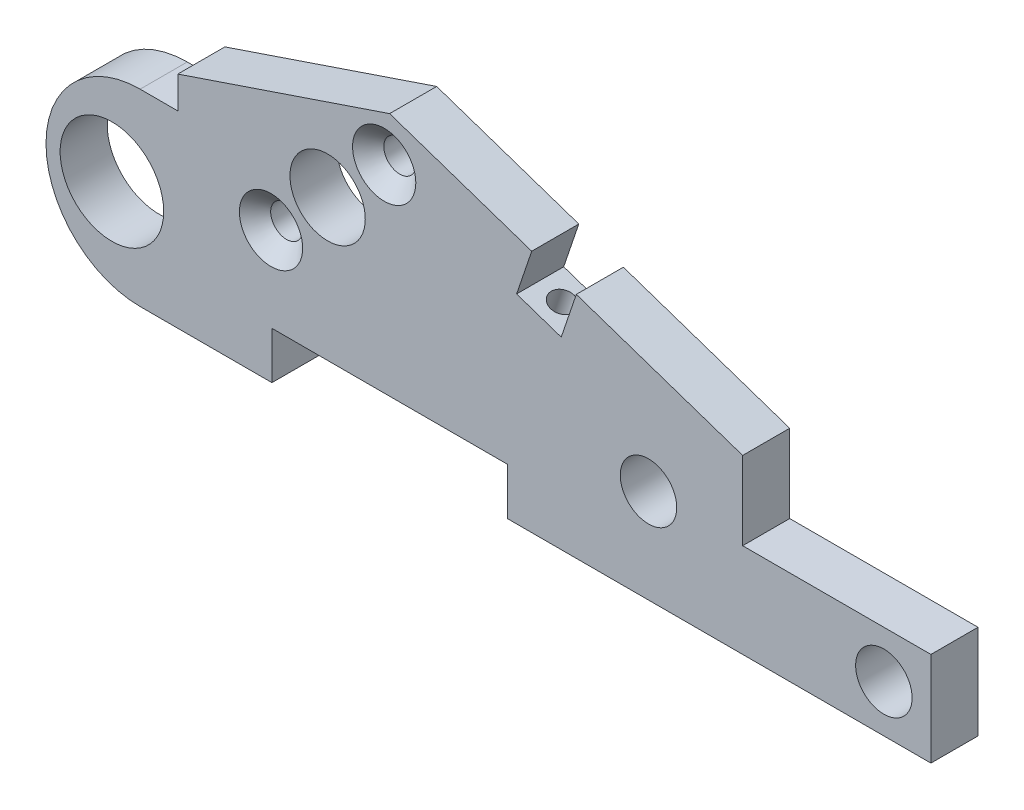
SolidWorks part; units mm, degrees
ref_plane "Front Plane" through (0, 0, 0) normal (0, 0, 1) x (1, 0, 0)
ref_plane "Top Plane" through (0, 0, 0) normal (0, 1, 0) x (1, 0, 0)
ref_plane "Right Plane" through (0, 0, 0) normal (1, 0, 0) x (0, 0, -1)
sketch "Sketch1" plane through (0, 0, 0) normal (0, 0, 1) x (1, 0, 0)
  line L0 (42.697, 5.7271) -> (5.197, 18.4194)
  line L1 (5.197, -12.5806) -> (5.197, 23.3572) construction
  line L2 (-31.303, -12.5806) -> (42.697, -12.5806)
  line L3 (42.697, -12.5806) -> (52.697, -12.5806)
  line L4 (52.697, -12.5806) -> (62.697, -12.5806)
  line L5 (-27.303, 7.4194) -> (-31.303, 7.4194)
  line L6 (-27.303, 7.4194) -> (-17.303, 7.4194)
  line L7 (-17.303, 7.4194) -> (-17.303, 10.8091)
  line L8 (-17.303, 10.8091) -> (5.197, 18.4194)
  line L9 (-31.303, 7.4194) -> (-31.303, -12.5806)
  line L10 (62.697, -12.5806) -> (62.697, -2.5806)
  line L11 (42.697, -2.5806) -> (42.697, 5.7271)
  line L12 (62.697, -2.5806) -> (52.697, -2.5806)
  line L16 (52.697, -2.5806) -> (42.697, -2.5806)
  dimension "D3" = 10
  dimension "D1" = 10
  dimension "D2" = 10
  dimension "D4" = 4
  dimension "D6" = 10
  dimension "D7" = 31
extrude "Boss-Extrude1" add sketch "Sketch1" along normal blind 5
sketch "Sketch2" plane through (0, 0, 5) normal (0, 0, 1) x (1, 0, 0)
  line L0 (-24.303, -2.5806) -> (-4.303, -2.5806) construction
  line L2 (-4.303, -2.5806) -> (-10.3134, -8.591) construction
  line L3 (-27.303, -2.5806) -> (-24.303, -2.5806) construction
  line L4 (-4.303, -2.5806) -> (-12.803, -2.5806) construction
  line L5 (-4.303, -2.5806) -> (1.7074, 3.4298) construction
  line L6 (-4.303, -2.5806) -> (4.197, -2.5806) construction
  line L7 (37.697, -2.5806) -> (32.697, -2.5806) construction
  circle A0 centre (-24.303, -2.5806) radius 25
  dimension "D6" = 8.5
  dimension "D8" = 50
  dimension "D1" = 3
  dimension "D2" = 20
  dimension "D3" = 8.5
  dimension "D4" = 8.5
  dimension "D5" = 8.5
  dimension "D7" = 5
hole_wizard "Ø11.0 (11) Diameter Hole1" positions "3DSketch2" profile "Sketch4" hole size "Ø11.0" standard "ISO"
sketch3d "3DSketch2"
  point P0 (-24.303, -2.5806, 5)
sketch "Sketch4" plane through (-24.303, -2.5806, 5) normal (1, 0, 0) x (0, -1, 0)
  line L0 (0, 0) -> (0, 28.3047)
  line L1 (0, 28.3047) -> (5.5, 25)
  line L2 (5.5, 25) -> (5.5, 0)
  line L5 (5.5, 0) -> (0, 0)
  line L10 (0, 28.3047) -> (-5.5, 25) construction
  line L11 (0, -6.35) -> (0, 107.95) construction
  dimension "Hole Dia." = 11
  dimension "Hole Depth" = 25
  dimension "Drill Angle" = 118
hole_wizard "Ø6.0mm Dowel Hole1" positions "3DSketch6" profile "Sketch9" hole size "Ø6.0" standard "ISO"
sketch3d "3DSketch6"
  point P0 (32.697, -2.5806, 5)
sketch "Sketch9" plane through (32.697, -2.5806, 5) normal (1, 0, 0) x (0, -1, 0)
  line L0 (0, 0) -> (0, 26.8026)
  line L1 (0, 26.8026) -> (3, 25)
  line L2 (3, 25) -> (3, 0)
  line L5 (3, 0) -> (0, 0)
  line L10 (0, 26.8026) -> (-3, 25) construction
  line L11 (0, -6.35) -> (0, 107.95) construction
  dimension "Hole Dia." = 6
  dimension "Hole Depth" = 25
  dimension "Drill Angle" = 118
sketch "Sketch22" plane through (0, 0, 0) normal (0, 0, -1) x (-1, 0, 0)
  line L0 (-37.697, -2.5806) -> (-17.697, -2.5806) construction
  line L1 (-17.697, -2.5806) -> (-17.697, -12.5806) construction
  line L3 (-17.697, -12.5806) -> (-17.697, -7.5806)
  line L4 (-17.697, -7.5806) -> (7.303, -7.5806)
  line L5 (7.303, -7.5806) -> (7.303, -12.5806)
  line L6 (7.303, -12.5806) -> (-17.697, -12.5806)
  dimension "D1" = 20
  dimension "D2" = 5
  dimension "D3" = 25
extrude "Cut-Extrude1" cut sketch "Sketch22" against normal blind 10
sketch "Sketch34" plane through (0, 0, 5) normal (0, 0, 1) x (1, 0, 0)
  line L0 (-1.3901, -12.5806) -> (-1.3901, 7.4194) construction
  line L2 (-24.303, -2.5806) -> (-1.3901, 7.4194) construction
  circle A0 centre (-24.303, -2.5806) radius 25 construction
  circle A1 centre (-1.3901, 7.4194) radius 12.5
  dimension "D1" = 25
hole_wizard "Ø8.0mm Dowel Hole2" positions "Sketch36" profile "Sketch35" hole size "Ø8.0" standard "ISO"
sketch "Sketch36" plane through (0, 0, 5) normal (0, 0, 1) x (1, 0, 0)
  point P0 (-1.3901, 7.4194)
sketch "Sketch35" plane through (-1.3901, 7.4194, 5) normal (1, 0, 0) x (0, -1, 0)
  line L0 (0, 0) -> (0, 22.4034)
  line L1 (0, 22.4034) -> (4, 20)
  line L2 (4, 20) -> (4, 0)
  line L5 (4, 0) -> (0, 0)
  line L10 (0, 22.4034) -> (-4, 20) construction
  line L11 (0, -6.35) -> (0, 107.95) construction
  dimension "Hole Dia." = 8
  dimension "Hole Depth" = 20
  dimension "Drill Angle" = 118
sketch "Sketch37" plane through (0, 0, 5) normal (0, 0, 1) x (1, 0, 0)
  line L0 (-1.3901, 7.4194) -> (-7.4005, 1.409) construction
  line L1 (-1.3901, 7.4194) -> (4.6203, 13.4298) construction
  dimension "D1" = 8.5
  dimension "D2" = 8.5
hole_wizard "CSK for M3 Hex Socket Countersunk Cap Screw1" positions "Sketch41" profile "Sketch40" countersink size "M3" standard "ISO" end condition through all
sketch "Sketch41" plane through (0, 0, 5) normal (0, 0, 1) x (1, 0, 0)
  point P0 (-7.4005, 1.409)
  point P3 (4.6203, 13.4298)
sketch "Sketch40" plane through (-7.4005, 1.409, 5) normal (1, 0, 0) x (0, -1, 0)
  line L0 (0, 0) -> (0, 5)
  line L1 (0, 5) -> (1.7, 5)
  line L2 (1.7, 5) -> (1.7, 1.66)
  line L3 (1.7, 1.66) -> (3.36, 0)
  line L5 (3.36, 0) -> (0, 0)
  line L6 (-1.7, 1.66) -> (-3.36, 0) construction
  line L11 (0, -6.35) -> (0, 107.95) construction
  dimension "Thru Hole Dia." = 3.4
  dimension "Thru Hole Depth" = 5
  dimension "Near C'Sink Dia." = 6.72
  dimension "Near C'Sink Angle" = 90
sketch "Sketch43" plane through (0, -7.5806, 0) normal (0, -1, 0) x (1, 0, 0)
  line L0 (5.197, 2.5) -> (-7.303, 2.5) construction
  line L3 (5.197, 2.5) -> (5.197, 0) construction
  line L4 (-7.303, 0) -> (17.697, 0) construction
  line L5 (-7.303, 5) -> (-7.303, 0) construction
  line L6 (-1.053, 2.5) -> (-1.053, 5) construction
  line L7 (17.697, 5) -> (-7.303, 5) construction
  line L8 (5.197, 2.5) -> (17.697, 2.5) construction
  line L9 (17.697, 5) -> (17.697, 0) construction
  line L10 (11.447, 2.5) -> (11.447, 5) construction
hole_wizard "M3 Tapped Hole1" positions "Sketch45" profile "Sketch44" tap size "M3" standard "ISO"
sketch "Sketch45" plane through (0, -7.5806, 0) normal (0, -1, 0) x (-1, 0, 0)
  point P0 (1.053, -2.5)
  point P3 (-11.447, -2.5)
sketch "Sketch44" plane through (-1.053, -7.5806, 2.5) normal (1, 0, 0) x (0, 0, -1)
  line L0 (0, 0) -> (0, 8.2511)
  line L1 (0, 8.2511) -> (1.25, 7.5)
  line L2 (1.25, 7.5) -> (1.25, 0)
  line L5 (1.25, 0) -> (0, 0)
  line L10 (0, 8.2511) -> (-1.25, 7.5) construction
  line L11 (0, -6.35) -> (0, 107.95) construction
  dimension "Tap Drill Dia." = 2.5
  dimension "Tap Drill Depth" = 7.5
  dimension "Drill Angle" = 118
cosmetic thread "Hole Thread1" parameters "D1"=6, "D2"=3
cosmetic thread "Hole Thread2" parameters "D1"=6, "D2"=3
sketch "Sketch46" plane through (0, 0, 5) normal (0, 0, 1) x (1, 0, 0)
  circle A0 centre (-24.303, -2.5806) radius 7.5
  dimension "D1" = 15
fillet "Fillet2" radius 10 rebuild error yes
fillet "Fillet3" radius 10 2 edges at (-31.303, -12.5806, 2.5) (-31.303, 7.4194, 2.5)
fillet "Fillet4" radius 5 rebuild error yes
sketch "Sketch47" plane through (0, 0, 0) normal (0, 0, -1) x (-1, 0, 0)
  line L0 (-36.9172, 7.6833) -> (-8.4019, 17.3346) construction
  line L1 (-8.4019, 17.3346) -> (-6.7989, 12.5986) construction
  line L2 (-6.7989, 12.5986) -> (-35.3143, 2.9472) construction
  line L3 (-35.3143, 2.9472) -> (-36.9172, 7.6833) construction
  line L4 (-21.0566, 7.7729) -> (-22.6596, 12.509) construction
  line L6 (-18.6885, 8.5744) -> (-20.2915, 13.3105)
  line L7 (-20.2915, 13.3105) -> (-25.0276, 11.7075)
  line L8 (-25.0276, 11.7075) -> (-23.4246, 6.9714)
  line L9 (-23.4246, 6.9714) -> (-18.6885, 8.5744)
  dimension "D1" = 5
  dimension "D2" = 2.5
  dimension "D3" = 2.5
  dimension "D4" = 5
extrude "Cut-Extrude2" cut sketch "Sketch47" against normal blind 10
hole_wizard "M3 Tapped Hole2" positions "Sketch51" profile "Sketch50" tap size "M3" standard "ISO"
sketch "Sketch51" plane through (4.5247, 13.3683, 0) normal (0.3206, 0.9472, 0) x (0.9472, -0.3206, 0)
  line L0 (19.9532, -2.5) -> (17.4532, -2.5023) construction
  line L1 (19.9532, -5) -> (19.9532, 0) construction
  line L2 (17.4532, -2.5023) -> (17.4532, 0) construction
  line L3 (19.9532, 0) -> (14.9532, 0) construction
  point P0 (17.4532, -2.5023)
sketch "Sketch50" plane through (21.0566, 7.7729, 2.5023) normal (0, 0, 1) x (-0.9472, 0.3206, 0)
  line L0 (0, 0) -> (0, 8.7511)
  line L1 (0, 8.7511) -> (1.25, 8)
  line L2 (1.25, 8) -> (1.25, 0)
  line L5 (1.25, 0) -> (0, 0)
  line L10 (0, 8.7511) -> (-1.25, 8) construction
  line L11 (0, -6.35) -> (0, 107.95) construction
  dimension "Tap Drill Dia." = 2.5
  dimension "Tap Drill Depth" = 8
  dimension "Drill Angle" = 118
cosmetic thread "Hole Thread3" parameters "D1"=6, "D2"=3
hole_wizard "Ø6.0 (6) Diameter Hole1" positions "Sketch53" profile "Sketch52" hole size "Ø6.0" standard "ISO" rebuild error yes
sketch "Sketch53" plane through (0, 0, 5) normal (0, 0, 1) x (1, 0, 0)
  line L0 (60.9166, 31.4884) -> (52.5437, 36.9561) construction
  line L1 (52.5437, 36.9561) -> (34.0595, 8.6505) construction
  point P0 (53.9963, 30.0358)
  dimension "D1" = 5
  dimension "D2" = 5
sketch "Sketch52" plane through (53.9963, 30.0358, 5) normal (1, 0, 0) x (0, -1, 0)
  line L0 (0, 0) -> (0, 26.8026)
  line L1 (0, 26.8026) -> (3, 25)
  line L2 (3, 25) -> (3, 0)
  line L5 (3, 0) -> (0, 0)
  line L10 (0, 26.8026) -> (-3, 25) construction
  line L11 (0, -6.35) -> (0, 107.95) construction
  dimension "Hole Dia." = 6
  dimension "Hole Depth" = 25
  dimension "Drill Angle" = 118
hole_wizard "Ø6.0 (6) Diameter Hole2" positions "Sketch55" profile "Sketch54" hole size "Ø6.0" standard "ISO"
sketch "Sketch55" plane through (0, 0, 0) normal (0, 0, -1) x (-1, 0, 0)
  line L0 (-62.697, -2.5806) -> (-42.697, -2.5806) construction
  line L3 (-62.697, -12.5806) -> (-62.697, -2.5806) construction
  point P0 (-57.697, -7.5806)
  dimension "D1" = 5
  dimension "D2" = 5
sketch "Sketch54" plane through (57.697, -7.5806, 0) normal (1, 0, 0) x (0, 1, 0)
  line L0 (0, 0) -> (0, 26.8026)
  line L1 (0, 26.8026) -> (3, 25)
  line L2 (3, 25) -> (3, 0)
  line L5 (3, 0) -> (0, 0)
  line L10 (0, 26.8026) -> (-3, 25) construction
  line L11 (0, -6.35) -> (0, 107.95) construction
  dimension "Hole Dia." = 6
  dimension "Hole Depth" = 25
  dimension "Drill Angle" = 118
